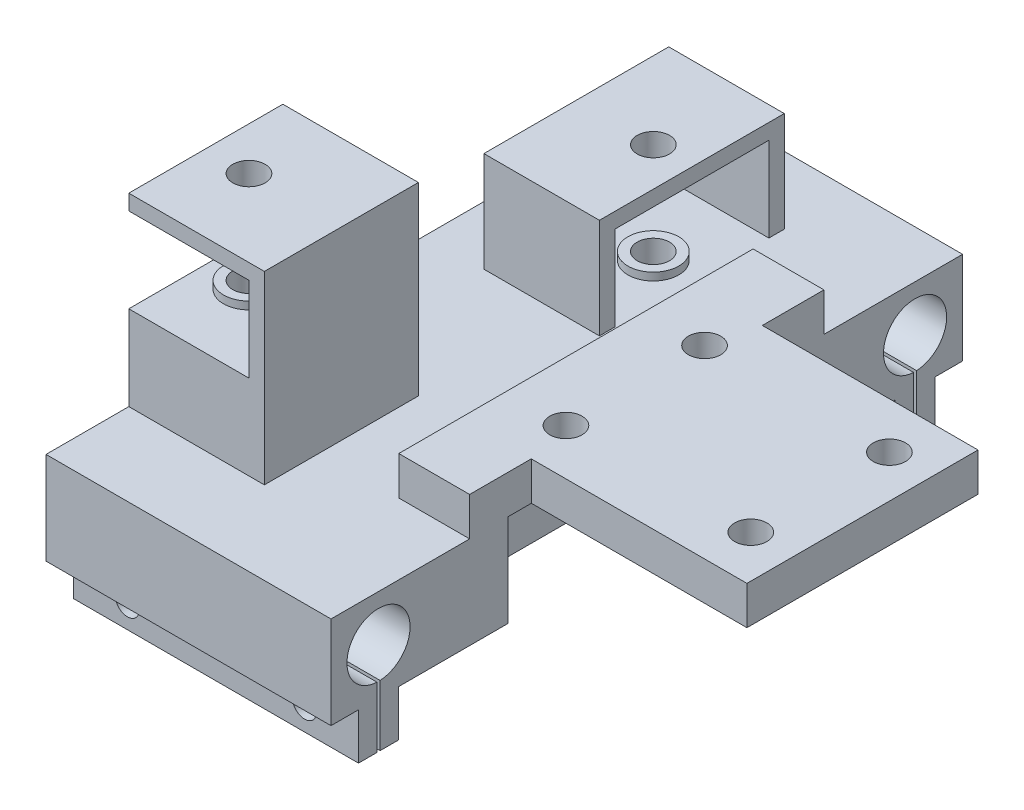
SolidWorks part; units mm, degrees
ref_plane "Спереди" through (0, 0, 0) normal (0, 0, 1) x (1, 0, 0)
ref_plane "Сверху" through (0, 0, 0) normal (0, 1, 0) x (1, 0, 0)
ref_plane "Справа" through (0, 0, 0) normal (1, 0, 0) x (0, 0, -1)
other "Configuration Table"
sketch "Sketch1" plane through (0, 0, 0) normal (0, 1, 0) x (1, 0, 0)
  line L0 (0, 0) -> (12, 0) construction
  line L1 (-17.5, -15) -> (17.5, -15)
  line L2 (-17.5, -15) -> (-17.5, 15)
  line L3 (-17.5, 15) -> (17.5, 15)
  line L4 (17.5, -15) -> (17.5, 15)
  line L5 (-17.5, -15) -> (17.5, 15) construction
  line L6 (-17.5, 15) -> (17.5, -15) construction
  line L7 (12, 0) -> (12, 9) construction
  line L8 (0, 0) -> (0, 10.8794) construction
  line L9 (-12, -9) -> (-12, -15) construction
  line L10 (-12, 9) -> (-12, 15) construction
  line L11 (-12, 9) -> (-17.5, 9) construction
  line L12 (12, 9) -> (17.5, 9) construction
  circle A0 centre (12, 9) radius 2.1
  circle A1 centre (12, -9) radius 2.1
  circle A2 centre (-12, -9) radius 2.1
  circle A3 centre (-12, 9) radius 2.1
  point P0 (0, 0)
  dimension "D3" = 4.2
  dimension "D1" = 35
  dimension "D2" = 30
  dimension "D4" = 18
  dimension "D5" = 24
extrude "Boss-Extrude1" add sketch "Sketch1" along normal blind 5
sketch "Sketch2" plane through (-17.5, 0, 0) normal (-1, 0, 0) x (0, 0, 1)
  line L1 (-15, 5) -> (15, 5)
  line L2 (-15, 5) -> (-15, -12)
  line L3 (-15, -12) -> (15, -12)
  line L4 (15, 5) -> (15, -12)
  dimension "D1" = 17
extrude "Boss-Extrude2" add sketch "Sketch2" along normal blind 5
sketch "Sketch3" plane through (17.5, 0, 0) normal (1, 0, 0) x (0, 0, -1)
  line L0 (15, -12) -> (-15, -12) construction
  line L1 (-41, 0) -> (41, 0)
  line L2 (0, 0) -> (0, -12)
  line L3 (-32.23, -12) -> (32.23, -12)
  line L4 (41, 0) -> (41, -12)
  line L5 (-34.83, -6) -> (34.83, -6) construction
  line L6 (34.83, -6) -> (34.83, -17.5071) construction
  line L7 (34.63, -18) -> (32.23, -18)
  line L9 (35.03, -12) -> (35.03, -18)
  line L10 (35.03, -18) -> (37.43, -18)
  line L11 (37.43, -12) -> (37.43, -18)
  line L12 (32.23, -12) -> (32.23, -18)
  line L14 (34.63, -12) -> (34.63, -18)
  line L15 (34.63, -12) -> (34.63, -10.0951)
  line L16 (35.03, -10.0951) -> (35.03, -12)
  line L18 (37.43, -12) -> (41, -12)
  line L19 (-34.83, -6) -> (-34.83, -17.5071) construction
  line L20 (-37.43, -12) -> (-41, -12)
  line L21 (-35.03, -10.0951) -> (-35.03, -12)
  line L22 (-34.63, -12) -> (-34.63, -10.0951)
  line L23 (-34.63, -12) -> (-34.63, -18)
  line L24 (-32.23, -12) -> (-32.23, -18)
  line L25 (-37.43, -12) -> (-37.43, -18)
  line L26 (-35.03, -18) -> (-37.43, -18)
  line L27 (-35.03, -12) -> (-35.03, -18)
  line L28 (-34.63, -18) -> (-32.23, -18)
  line L29 (-41, 0) -> (-41, -12)
  arc A0 (35.03, -10.0951) -> (34.63, -10.0951) centre (34.83, -6) ccw
  arc A1 (-35.03, -10.0951) -> (-34.63, -10.0951) centre (-34.83, -6) cw
  point P22 (0, -6)
  dimension "D2" = 8.2
  dimension "D1" = 41
  dimension "D3" = 6
  dimension "D4" = 0.2
  dimension "D5" = 2.4
  dimension "D6" = 69.66
extrude "Boss-Extrude3" add sketch "Sketch3" against normal blind 37 from offset 28 contours A1 L22 L23 L28 L24 L3 L12 L7 L14 L15 A0 L16 L9 L10 L11 L18 L4 L1 L29 L20 L25 L26 L27 L21 offset against normal yes
sketch "Sketch5" plane through (-22.5, 0, 0) normal (-1, 0, 0) x (0, 0, 1)
  line L0 (0, 0) -> (0, -11.9864) construction
  line L1 (15, 0) -> (15, 5) construction
  line L2 (-18, -12) -> (18, -12)
  line L3 (-18, -12) -> (-18, 0.0136)
  line L4 (-18, 0.0136) -> (18, 0.0136)
  line L5 (18, -12) -> (18, 0.0136)
  line L6 (-18, -12) -> (18, 0.0136) construction
  line L7 (-18, 0.0136) -> (18, -12) construction
  line L8 (32.23, -12) -> (-32.23, -12) construction
  point P2 (0, -5.9932)
  dimension "D1" = 3
extrude "Cut-Extrude1" cut sketch "Sketch5" against normal up to next from offset 4.5 offset against normal yes
sketch "Sketch6" plane through (0, 5, 0) normal (0, 1, 0) x (1, 0, 0)
  line L0 (-22.5, 0) -> (-22.5, -20.25) construction
  line L1 (-22.5, 15) -> (-22.5, -15) construction
  line L2 (-22.5, -20.25) -> (-29.9, -20.25) construction
  line L3 (-22.5, 0) -> (-22.5, 20.25) construction
  line L4 (-22.5, 20.25) -> (-41.9, 20.25) construction
  line L5 (-29.9, -20.25) -> (-20.4, -20.25) construction
  line L7 (-20.4, -20.25) -> (-22.5, -20.25)
  line L8 (-20.4, -20.25) -> (-20.4, 15)
  line L9 (-20.4, 15) -> (-22.5, 15)
  line L10 (-22.5, -20.25) -> (-22.5, 15)
  dimension "D3" = 9.5
  dimension "D1" = 20.25
  dimension "D2" = 7.4
  dimension "D4" = 19.4
extrude "Cut-Extrude2" cut sketch "Sketch6" against normal up to surface (5 mm away) up to face at (-21.1667, 0, 0)
sketch "Sketch7" plane through (0, 5, 0) normal (0, 1, 0) x (1, 0, 0)
  line L0 (-20.4, 0) -> (-20.4, -20.25) construction
  line L2 (-20.4, -20.25) -> (-41.9, -20.25) construction
  line L3 (-20.4, 0) -> (-20.4, 20.25) construction
  line L4 (-20.4, 20.25) -> (-29.9, 20.25) construction
  line L6 (-20.4, -15) -> (-20.4, 15) construction
  circle A0 centre (-41.9, -20.25) radius 2.1
  circle A1 centre (-29.9, 20.25) radius 2.1
  point P10 (-20.4, 0)
  dimension "D4" = 4.2
  dimension "D1" = 20.25
  dimension "D2" = 21.5
  dimension "D3" = 9.5
sketch "Sketch9" plane through (0, 0, 0) normal (0, 1, 0) x (1, 0, 0)
  line L0 (-10.5, 18) -> (-10.5, 41) construction
  line L1 (-10.5, 23) -> (-20.4, 23)
  line L2 (-10.5, 23) -> (-10.5, 15)
  line L3 (-10.5, 15) -> (-20.4, 15)
  line L4 (-20.4, 23) -> (-20.4, 15)
  line L5 (-10.5, -41) -> (-10.5, -18) construction
  line L6 (-10.5, -23) -> (-20.4, -23)
  line L7 (-10.5, -23) -> (-10.5, -15)
  line L8 (-10.5, -15) -> (-20.4, -15)
  line L9 (-20.4, -23) -> (-20.4, -15)
  line L10 (-20.4, -15) -> (-20.4, 15) construction
  dimension "D1" = 8
  dimension "D2" = 8
extrude "Boss-Extrude5" add sketch "Sketch9" along normal up to surface (5 mm away) up to face at (-1.45, 5, 0)
sketch "Sketch10" plane through (0, 5, 0) normal (0, 1, 0) x (1, 0, 0)
  line L0 (-20.4, -23) -> (-10.5, -23) construction
  line L1 (-20.4, 23) -> (-19.7, 23)
  line L2 (-20.4, 23) -> (-20.4, -23)
  line L3 (-20.4, -23) -> (-19.7, -23)
  line L4 (-19.7, 23) -> (-19.7, -23)
  dimension "D1" = 0.7
extrude "Cut-Extrude4" cut sketch "Sketch10" against normal up to surface (5 mm away) up to face at (-22.225, 0, 0)
extrude "Cut-Extrude5" cut sketch "Sketch7" against normal up to next
sketch "Sketch11" plane through (0, 0, 0) normal (0, 1, 0) x (1, 0, 0)
  line L0 (-29.9, 20.25) -> (-29.9, 30.25) construction
  line L1 (-29.9, 20.25) -> (-39.9, 20.25) construction
  line L2 (-41.9, -20.25) -> (-29.9, -20.25) construction
  line L7 (-41.9, -20.25) -> (-41.9, -10.25) construction
  line L8 (-47.5, -41) -> (-47.5, 41) construction
  line L9 (-29.9, -10.25) -> (-47.5, -10.25)
  line L10 (-29.9, -10.25) -> (-29.9, -30.25)
  line L11 (-29.9, -30.25) -> (-47.5, -30.25)
  line L12 (-47.5, -10.25) -> (-47.5, -30.25)
  line L14 (-39.9, 30.25) -> (-24.9, 30.25)
  line L15 (-39.9, 30.25) -> (-39.9, 32.25)
  line L16 (-39.9, 32.25) -> (-24.9, 32.25)
  line L17 (-24.9, 30.25) -> (-24.9, 32.25)
  line L18 (-39.9, 10.25) -> (-24.9, 10.25)
  line L19 (-39.9, 10.25) -> (-39.9, 8.25)
  line L20 (-39.9, 8.25) -> (-24.9, 8.25)
  line L21 (-24.9, 10.25) -> (-24.9, 8.25)
  dimension "D1" = 10
  dimension "D2" = 10
  dimension "D3" = 10
  dimension "D4" = 2
  dimension "D5" = 10
  dimension "D6" = 12
  dimension "D7" = 20
  dimension "D8" = 2
  dimension "D9" = 5
extrude "Boss-Extrude6" add sketch "Sketch11" along normal blind 11
sketch "Sketch12" plane through (0, 11, 0) normal (0, 1, 0) x (1, 0, 0)
  line L5 (-39.9, 32.25) -> (-24.9, 32.25)
  line L6 (-39.9, 32.25) -> (-39.9, 8.25)
  line L7 (-39.9, 8.25) -> (-24.9, 8.25)
  line L8 (-24.9, 32.25) -> (-24.9, 8.25)
extrude "Boss-Extrude8" add sketch "Sketch12" along normal blind 2
sketch "Sketch13" plane through (0, 11, 0) normal (0, 1, 0) x (1, 0, 0)
  line L0 (-47.5, -30.25) -> (-29.9, -30.25) construction
  line L1 (-29.9, -10.25) -> (-31.9, -10.25)
  line L2 (-29.9, -10.25) -> (-29.9, -30.25)
  line L3 (-29.9, -30.25) -> (-31.9, -30.25)
  line L4 (-31.9, -10.25) -> (-31.9, -30.25)
  dimension "D1" = 2
extrude "Boss-Extrude9" add sketch "Sketch13" along normal blind 11
sketch "Sketch14" plane through (0, 22, 0) normal (0, 1, 0) x (1, 0, 0)
  line L1 (-29.9, -30.25) -> (-47.5, -30.25)
  line L2 (-29.9, -30.25) -> (-29.9, -10.25)
  line L3 (-29.9, -10.25) -> (-47.5, -10.25)
  line L4 (-47.5, -30.25) -> (-47.5, -10.25)
extrude "Boss-Extrude10" add sketch "Sketch14" along normal blind 2
sketch "Sketch15" plane through (0, -12, 0) normal (0, -1, 0) x (1, 0, 0)
  circle A0 centre (-29.9, -20.25) radius 2.1
  circle A1 centre (-41.9, 20.25) radius 2.1
extrude "Cut-Extrude6" cut sketch "Sketch15" against normal up to surface (36 mm away) up to face at (-38.7, 24, 20.25)
sketch "Sketch16" plane through (0, -12, 0) normal (0, -1, 0) x (1, 0, 0)
  circle A0 centre (-41.9, 20.25) radius 4
  circle A1 centre (-29.9, -20.25) radius 4.5
  dimension "D1" = 8
  dimension "D2" = 9
extrude "Cut-Extrude7" cut sketch "Sketch16" against normal blind 8
sketch "Sketch17" plane through (0, 24, 0) normal (0, 1, 0) x (1, 0, 0)
  circle A0 centre (-41.9, -20.25) radius 2.1
  circle A1 centre (-41.9, -20.25) radius 3.3
  dimension "D1" = 1.2
extrude "Boss-Extrude11" add sketch "Sketch17" against normal blind 1 from surface starting at face at (-41.9, 22, 22.35)
extrude "Boss-Extrude12" add sketch "Sketch17<2>" along normal blind 1 from surface starting at face at (-41.9, 11, 18.15)
sketch "Sketch17<2>" plane through (0, 24, 0) normal (0, 1, 0) x (1, 0, 0) same geometry as "Sketch17"
sketch "Sketch18" plane through (0, 13, 0) normal (0, 1, 0) x (1, 0, 0)
  circle A0 centre (-29.9, 20.25) radius 2.1
  circle A1 centre (-29.9, 20.25) radius 3.3
  dimension "D1" = 1.2
extrude "Boss-Extrude13" add sketch "Sketch18" against normal blind 1 from surface starting at face at (-29.9, 11, -18.15)
extrude "Boss-Extrude14" add sketch "Sketch18<2>" along normal blind 1 from surface starting at face at (-27.6, 0, 6.75)
sketch "Sketch18<2>" plane through (0, 13, 0) normal (0, 1, 0) x (1, 0, 0) same geometry as "Sketch18"
sketch "Sketch19" plane through (0, 0, 37.43) normal (0, 0, 1) x (1, 0, 0)
  line L0 (-10.5, -15) -> (-47.5, -15) construction
  line L1 (-10.5, -12) -> (-10.5, -18) construction
  line L2 (-47.5, -12) -> (-47.5, -18) construction
  line L3 (-29, -15) -> (-29, -18) construction
  line L4 (-47.5, -18) -> (-10.5, -18) construction
  circle A0 centre (-40.5, -15) radius 1.55
  circle A1 centre (-17.5, -15) radius 1.55
  dimension "D2" = 3.1
  dimension "D1" = 7
extrude "Cut-Extrude8" cut sketch "Sketch19" against normal through all
